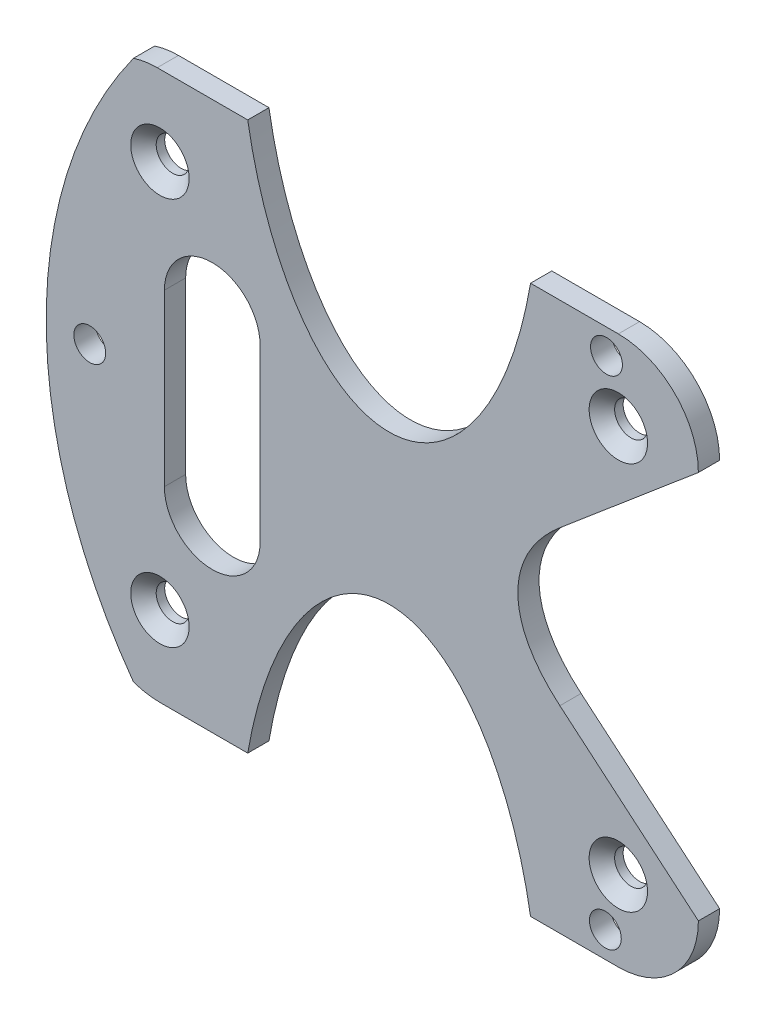
SolidWorks part; units mm, degrees
note: The reader was unsure of these and kept them because the rebuilt part matched: shared geometry of "Esquisse14<5>".
ref_plane "Plan de face" through (0, 0, 0) normal (0, 0, 1) x (1, 0, 0)
ref_plane "Plan de dessus" through (0, 0, 0) normal (0, 1, 0) x (1, 0, 0)
ref_plane "Plan de droite" through (0, 0, 0) normal (1, 0, 0) x (0, 0, -1)
sketch "Esquisse1" plane through (0, 0, 0) normal (0, 0, 1) x (1, 0, 0)
  line L8 (5, 2.54) -> (5, 39.116)
  line L9 (-2.54, 46.656) -> (-45.974, 46.656)
  line L10 (-53.26, 39.37) -> (-53.26, 2.54)
  line L11 (-45.72, -5) -> (-2.54, -5)
  arc A8 (5, 39.116) -> (-2.54, 46.656) centre (-2.54, 39.116) ccw
  arc A9 (-45.974, 46.656) -> (-53.26, 39.37) centre (-45.974, 39.37) ccw
  arc A10 (-53.26, 2.54) -> (-45.72, -5) centre (-45.72, 2.54) ccw
  arc A11 (-2.54, -5) -> (5, 2.54) centre (-2.54, 2.54) ccw
extrude "Boss.-Extru.1" add sketch "Esquisse1" along normal blind 2
sketch "Esquisse14" plane through (0, 0, 0) normal (0, 0, 1) x (1, 0, 0)
  line L0 (-40.7896, 12.8151) -> (-40.7896, 28.8409) construction
  line L1 (-8.0454, 28.0915) -> (5, 39.116)
  line L2 (-8.0477, 13.5704) -> (5, 2.54)
  line L3 (-39.5876, 20.828) -> (-53.8274, 20.828) construction
  line L8 (-45.2988, 12.8151) -> (-45.2988, 28.8409)
  line L9 (-36.2804, 12.8151) -> (-36.2804, 28.8409)
  line L13 (-53.26, 19.7477) -> (-53.26, 4.5581)
  line L14 (-45.72, -5) -> (-2.54, -5)
  line L15 (5, 2.54) -> (5, 39.116)
  line L16 (-2.54, 46.656) -> (-45.974, 46.656)
  line L17 (-53.26, 37.1652) -> (-53.26, 22.1024)
  line L23 (-53.2395, 39.9168) -> (-53.9005, 35.482)
  line L24 (-53.8801, 6.1843) -> (-53.2103, 1.6757)
  line L25 (-53.26, 4.5581) -> (-53.26, 19.7477)
  line L26 (-53.26, 22.1024) -> (-53.26, 37.1652)
  arc A0 (-48.2122, 46.3037) -> (-48.2163, -4.5748) centre (-12.9481, 20.8616) ccw
  arc A1 (-45.2988, 12.8151) -> (-36.2804, 12.8151) centre (-40.7896, 12.8151) ccw
  arc A2 (-36.2804, 28.8409) -> (-45.2988, 28.8409) centre (-40.7896, 28.8409) ccw
  arc A10 (-53.26, 19.7477) -> (-53.26, 22.1024) centre (-52.3305, 20.925) ccw
  arc A11 (-53.2103, 1.6757) -> (-45.72, -5) centre (-45.72, 2.54) ccw
  arc A12 (-2.54, -5) -> (5, 2.54) centre (-2.54, 2.54) ccw
  arc A13 (5, 39.116) -> (-2.54, 46.656) centre (-2.54, 39.116) ccw
  arc A14 (-45.974, 46.656) -> (-53.2395, 39.9168) centre (-45.974, 39.37) ccw
  arc A21 (-53.26, 22.1024) -> (-53.26, 19.7477) centre (-52.3305, 20.925) ccw
  ellipse E0 centre (-24.13, 55.3259) end of major axis (-24.13, 27.8487) minor radius 14.0367 (-37.4497, 46.656) -> (-10.8103, 46.656) ccw
  ellipse E1 centre (-24.13, -13.6699) end of major axis (-24.13, 13.8073) minor radius 14.0367 (-37.4497, -5) -> (-10.8103, -5) cw
  ellipse E2 centre (15.4694, 20.83) end of major axis (-12.0079, 20.83) minor radius 14.0367 (-8.0477, 13.5704) -> (-8.0454, 28.0915) cw
  point P47 (-40.7896, 20.828)
sketch "Esquisse15" plane through (0, 0, 0) normal (0, 0, 1) x (1, 0, 0)
  circle A6 centre (-52.3305, 20.925) radius 1.5
  circle A7 centre (-3.7635, -2.5517) radius 1.5
  circle A8 centre (-3.6584, 44.3104) radius 1.5
  dimension "D1" = 3
  dimension "D2" = 3
  dimension "D3" = 3
hole_wizard "Fraisage pour vis à tête fraisée bombée M2.51" positions "Esquisse3D2" profile "Esquisse16" countersink size "M2.5" standard "JIS" end condition through all
sketch3d "Esquisse3D2"
  line L0 (-45.72, -5, 2) -> (-2.54, -5, 2) construction
  line L1 (5, 2.54, 2) -> (5, 39.116, 2) construction
  line L2 (-53.26, 39.37, 2) -> (-53.26, 2.54, 2) construction
  line L3 (-2.54, 46.656, 2) -> (-45.974, 46.656, 2) construction
  point P0 (-2.54, 2.54, 2)
  point P2 (-2.54, 39.116, 2)
  point P4 (-45.72, 39.116, 2)
  point P6 (-45.72, 2.54, 2)
  dimension "D1" = 7.54
  dimension "D2" = 7.54
  dimension "D3" = 7.54
  dimension "D4" = 7.54
sketch "Esquisse16" plane through (-2.54, 2.54, 2) normal (1, 0, 0) x (0, -1, 0)
  line L0 (0, 0) -> (0, 2)
  line L1 (0, 2) -> (1.55, 2)
  line L2 (1.55, 2) -> (1.55, 1.2)
  line L3 (1.55, 1.2) -> (2.75, 0)
  line L5 (2.75, 0) -> (0, 0)
  line L6 (-1.55, 1.2) -> (-2.75, 0) construction
  line L11 (0, -6.35) -> (0, 107.95) construction
  dimension "Diamètre du perçage jusqu'au prochain" = 3.1
  dimension "Profondeur du perçage jusqu'au prochain" = 2
  dimension "Diamètre du fraisage entrant" = 5.5
  dimension "Angle du fraisage entrant" = 90
extrude "Enlèv. mat.-Extru.5" cut sketch "Esquisse15" along normal blind 2 contours A8 | A6 | A7
extrude "Boss.-Extru.3" add sketch "Esquisse14" along normal blind 2 contours A21 L17 A0 L13
extrude "Enlèv. mat.-Extru.4" cut sketch "Esquisse14<5>" along normal blind 2 contours A0 A14 L23 | L16 E0 | L3 L15 L1 E2 | L15 L3 E2 L2 | E1 L14 | L24 A11 A0 | L9 A2 L8 A1
sketch "Esquisse14<5>" plane through (0, 0, 0) normal (0, 0, 1) x (1, 0, 0) same geometry as "Esquisse14"
